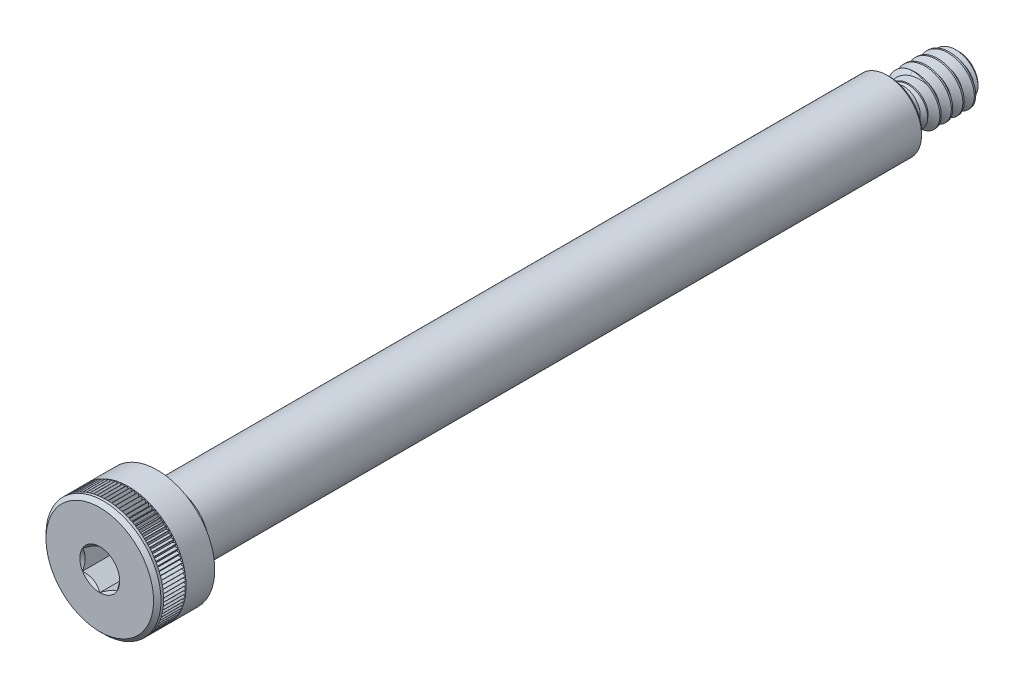
SolidWorks part; units mm, degrees
other "DetailItem1"
other "DetailItem2"
other "DetailItem5"
other "DetailItem6"
ref_plane "Front" through (0, 0, 0) normal (0, 0, 1) x (1, 0, 0)
ref_plane "Top" through (0, 0, 0) normal (0, 1, 0) x (1, 0, 0)
ref_plane "Right" through (0, 0, 0) normal (1, 0, 0) x (0, 0, -1)
sketch "Sketch1" plane through (0, 0, 0) normal (1, 0, 0) x (0, 0, -1)
  line L0 (0, 3.9688) -> (3.9688, 3.9688) construction
  line L1 (3.9688, 3.9688) -> (3.9688, 2.1828) construction
  line L2 (5.1594, 2.3812) -> (54.5147, 2.3813) construction
  line L3 (5.1594, -2.3813) -> (54.5147, -2.3812) construction
  line L4 (54.5147, 1.7526) -> (59.2772, 1.7526) construction
  line L5 (59.2772, 1.7526) -> (59.2772, 0) construction
  line L6 (54.5147, 0) -> (0, 0) construction
  line L7 (0, 0) -> (0, 3.9688) construction
  line L8 (0, 3.9688) -> (0, -3.9688) construction
  line L9 (59.2772, 1.7526) -> (59.2772, -1.7526) construction
  line L10 (54.5147, 2.3813) -> (54.5147, -2.3812) construction
  line L11 (59.2772, -1.7526) -> (57.5995, -1.7526) construction
  line L12 (54.5147, 2.3813) -> (54.5147, 0) construction
  line L13 (3.9688, 2.1828) -> (4.9609, 2.1828) construction
  line L14 (4.9609, 2.1828) -> (5.1594, 2.3812) construction
  line L15 (59.2772, 0) -> (54.5147, 0) construction
  line L16 (4.9609, -2.1828) -> (5.1594, -2.3813) construction
  line L17 (3.9688, -2.1828) -> (4.9609, -2.1828) construction
  line L18 (0, -3.9688) -> (3.9688, -3.9687) construction
  line L19 (3.9688, -3.9687) -> (3.9688, -2.1828) construction
  line L20 (59.2772, 2.3812) -> (58.4835, 2.3812) construction
  line L21 (59.2772, -2.3812) -> (58.0866, -2.3812) construction
  line L22 (59.2772, 0) -> (64.0397, 0) construction
  line L23 (29.2418, 0) -> (29.2417, 2.351) construction
  line L24 (59.2772, -2.3812) -> (59.2772, 2.3812) construction
  point P2 (5.2324, 0)
  point P8 (58.0866, -1.7526)
  point P12 (54.5147, 0)
  point P15 (53.2511, 0)
  point P31 (7.6333, 0)
  point P32 (50.8502, 0)
  point P34 (59.2772, 0)
  dimension "Head Dia" = 7.9375
  dimension "Head Ht" = 3.9688
  dimension "Thread Lg" = 4.7625
  dimension "Thread Dia" = 3.5052
  dimension "Shoulder Dia" = 4.7625
  dimension "D1" = 1.1906
  dimension "D2" = 1.6778
  dimension "D3" = 135
  dimension "D4" = 0.9922
  dimension "D5" = 0.1984
  dimension "Shoulder Lg Max" = 50.546
  dimension "D6" = 25.273
  dimension "D7" = 48.0187
  dimension "D8" = 43.2168
  dimension "Pitch" = 0.7937
sketch "Sketch13" plane through (0, 0, 0) normal (1, 0, 0) x (0, 0, -1)
  line L0 (0, 0) -> (0, 3.9688)
  line L1 (0, 3.9688) -> (3.9688, 3.9688)
  line L2 (3.9688, 3.9688) -> (3.9688, 2.1828)
  line L3 (3.9688, 2.1828) -> (4.9609, 2.1828)
  line L4 (54.5147, 0) -> (54.5147, 2.1828)
  line L5 (4.9609, 2.1828) -> (5.1594, 2.3812)
  line L7 (54.5147, 2.3813) -> (54.5147, 0) construction
  line L8 (54.5147, 2.3813) -> (54.5147, -2.3812) construction
  line L9 (54.5147, 0) -> (0, 0) construction
  line L10 (54.5147, 2.1828) -> (54.3163, 2.3812)
  line L12 (5.1594, 2.3812) -> (54.3163, 2.3812)
  line L13 (0, 0) -> (54.5147, 0)
  dimension "D1" = 4.7625
  dimension "D2" = 45
revolve "Revolve1" add sketch "Sketch13" angle 360 about L9
sketch "Sketch12" plane through (0, 0, -54.5147) normal (0, 0, -1) x (-1, 0, 0)
  circle A0 centre (0, 0) radius 1.7526
extrude "Boss-Extrude1" add sketch "Sketch12" along normal up to vertex (4.7625 mm away) up to point (0, 0, -59.2772)
ref_plane "Plane1" through (0, 0, -59.2772) normal (0, 0, 1) x (1, 0, 0)
sketch "Sketch3" plane through (0, 0, -59.2772) normal (0, 0, 1) x (1, 0, 0)
  circle A0 centre (0, 0) radius 1.7526
sketch "Sketch5" plane through (0, 0, 0) normal (1, 0, 0) x (0, 0, -1)
  line L0 (54.5147, 1.7526) -> (56.0807, 1.7526)
  line L1 (56.0807, 1.7526) -> (55.4672, 1.1392)
  line L2 (55.4672, 1.1392) -> (54.5147, 1.1392)
  line L3 (54.5147, 1.7526) -> (54.5147, 1.1392)
  line L4 (54.5147, 1.7526) -> (59.2772, 1.7526) construction
  line L5 (54.5147, 2.3813) -> (54.5147, 0) construction
  line L6 (54.5147, 2.3813) -> (54.5147, -2.3812) construction
  line L7 (59.2772, 0) -> (54.5147, 0) construction
  line L8 (59.2772, -1.7526) -> (59.2772, 1.7526) construction
  dimension "D4" = 0.9525
  dimension "D1" = 45
  dimension "D3" = 1.1392
revolve "Cut-Revolve1" cut sketch "Sketch5" angle 360 mid plane about L6
chamfer "Chamfer1" distance 0.4381 angle 45 1 edges at (-1.7526, 0, -59.2772)
chamfer "Chamfer2" distance 0.258 angle 45 1 edges at (-3.9688, 0, 0)
fillet "Fillet1" radius 0.1984 1 edges at (0, 1.1392, -54.5147)
sketch "Sketch10" plane through (0, 0, 0) normal (1, 0, 0) x (0, 0, -1)
  line L0 (0.258, 0) -> (3.7108, 0) construction
  line L1 (3.9688, -3.9688) -> (3.9688, 3.9688) construction
  line L2 (0.258, -3.9688) -> (0.258, 3.9688) construction
  line L3 (0.258, 0) -> (0, 0) construction
  line L4 (3.7108, 0) -> (3.9688, 0) construction
  point P6 (1.9844, 0)
  dimension "D1" = 3.4528
ref_plane "Plane2" through (0, 0, -1.9844) normal (0, 0, 1) x (1, 0, 0)
sketch "Sketch8" plane through (0, 0, 0) normal (0, 0, 1) x (1, 0, 0)
  line L1 (1.1906, 0.6874) -> (0, 1.3748)
  line L2 (0, 1.3748) -> (-1.1906, 0.6874)
  line L3 (-1.1906, 0.6874) -> (-1.1906, -0.6874)
  line L4 (-1.1906, -0.6874) -> (0, -1.3748)
  line L5 (0, -1.3748) -> (1.1906, -0.6874)
  line L6 (1.1906, -0.6874) -> (1.1906, 0.6874)
  circle A0 centre (0, 0) radius 1.1906 construction
  dimension "Hex" = 2.3813
extrude "Cut-Extrude2" cut sketch "Sketch8" against normal blind 1.9844
sketch "Sketch9" plane through (0, 0, 0) normal (0, 0, 1) x (1, 0, 0)
  circle A0 centre (0, 0) radius 1.3748
extrude "Cut-Extrude4" cut sketch "Sketch9" against normal blind 1.9844 draft 45
sketch "reference 1" plane through (0, 0, -3.9688) normal (0, 0, -1) x (-1, 0, 0)
  circle A1 centre (0, 0) radius 3.9688
curve "Helix/Spiral1" pitch 0.7937 height 4.4847 radius 1.7526 centre (0, 0, -59.2772) axis (0, 0, 1) start towards (0, 1, 0)
ref_plane "Plane3" through (0, 0, -54.5147) normal (0, 0, 1) x (1, 0, 0)
split "Split1" trim tools "Plane3" bodies to split 118 resulting bodies 127 128
sketch "Sketch4" plane through (0, 0, 0) normal (1, 0, 0) x (0, 0, -1)
  line L0 (59.6245, 1.8385) -> (59.6245, 1.7526) construction
  line L1 (59.6245, 1.1511) -> (60.0214, 1.8385) construction
  line L3 (60.0214, 1.8385) -> (59.2276, 1.8385) construction
  line L4 (59.2276, 1.8385) -> (59.6245, 1.1511) construction
  line L5 (59.6245, 1.1511) -> (59.6245, 1.237) construction
  line L6 (59.2772, 1.7526) -> (59.9718, 1.7526) construction
  line L7 (59.5749, 1.237) -> (59.6741, 1.237) construction
  line L8 (59.2524, 1.7956) -> (59.9966, 1.7956) construction
  line L9 (59.2524, 1.7956) -> (59.9966, 1.7956)
  line L10 (59.9966, 1.7956) -> (59.6741, 1.237)
  line L11 (59.6741, 1.237) -> (59.5749, 1.237)
  line L12 (59.5749, 1.237) -> (59.2524, 1.7956)
  circle A0 centre (59.6245, 1.6094) radius 0.2291 construction
  point P12 (59.6245, 1.7526)
  point P16 (59.6245, 1.237)
  point P19 (59.6245, 1.7956)
  dimension "D1" = 0.7937
  dimension "D2" = 0.0992
sweep "Cut-Sweep1" cut profiles "Sketch4" path "Helix/Spiral1" align with end faces yes
combine bodies "Combine1" operation type add bodies to combine 129 127
sketch "Sketch11" plane through (0, 0, -1.9844) normal (0, 0, 1) x (1, 0, 0)
  line L0 (0, 3.7624) -> (0, 3.9688) construction
  line L1 (0, 3.7624) -> (0.1192, 3.9688)
  line L2 (0, 3.7624) -> (-0.1192, 3.9688)
  line L3 (-0.1192, 3.9688) -> (0.1192, 3.9688)
  line L4 (0, 0) -> (-0.1192, 3.9688) construction
  line L5 (0.1192, 3.9688) -> (0, 0) construction
  circle A2 centre (0, 0) radius 3.9688 construction
  point P8 (2.3908, 0.7309)
  dimension "D1" = 0.2064
  dimension "D2" = 3.439
extrude "Cut-Extrude5" cut sketch "Sketch11" along normal blind 1.5538
pattern_circular "CirPattern1" count 99 over 360 about axis through (0, 0, -54.5147) along (0, 0, 1) of "Cut-Extrude5" reverse direction yes
equation "\"D3@Helix/Spiral1\"=\"D2@Sketch5\" + (\"D4@Helix/Spiral1\"*0.85)"
equation "\"D1@Chamfer1\" = \"Thread Dia@Sketch1\" * .125"
equation "\"D1@Cut-Extrude2\"= \"Head Ht@Sketch1\" * .5"
equation "\"D1@Cut-Extrude4\" = \"D1@Cut-Extrude2\""
equation "\"D1@Chamfer2\"=\"Head Dia@Sketch1\" * .0325"
equation "\"D1@Sketch1\"=\"Pitch@Sketch1\"*1.5"
equation "\"D1@Sketch11\"=\"D1@Chamfer2\"*.8"
equation "\"D1@Sketch4\"=\"D4@Helix/Spiral1\""
equation "\"D2@Sketch4\"=\"D1@Sketch4\"/8"
equation "\"D4@Sketch5\"=\"Thread Lg@Sketch1\"*0.2"
equation "\"D3@Sketch5\"=(\"Thread Dia@Sketch1\"*0.65)/2"
equation "\"D1@Fillet1\"=\"D4@Helix/Spiral1\"*.25"
equation "\"D1@Cut-Extrude5\"=\"D1@Sketch10\"*.45"
equation "\"D1@CirPattern1\"=(360/(\"D2@Sketch11\"))-6"
equation "\"D1@Sketch13\"=\"Shoulder Dia@Sketch1\""
equation "\"D5@Sketch1\"=\"Head Dia@Sketch1\"*0.025"
equation "\"D6@Sketch1\"=\"Shoulder Lg Max@Sketch1\"/2"
equation "\"D7@Sketch1\"=\"Shoulder Lg Max@Sketch1\"*0.95"
equation "\"D8@Sketch1\"=\"D7@Sketch1\"*0.9"
equation "\"D4@Helix/Spiral1\"=\"Pitch@Sketch1\""
equation "\"D4@Sketch1\"=\"Head Ht@Sketch1\"*0.25"
